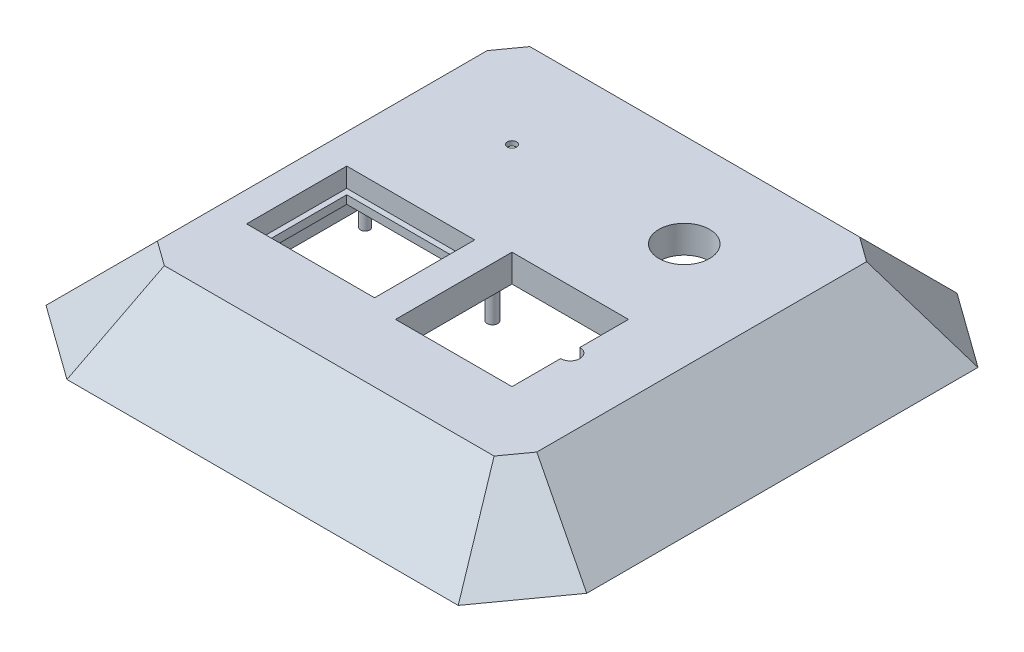
SolidWorks part; units mm, degrees
ref_plane "Front Plane" through (0, 0, 0) normal (0, 0, 1) x (1, 0, 0)
ref_plane "Top Plane" through (0, 0, 0) normal (0, 1, 0) x (1, 0, 0)
ref_plane "Right Plane" through (0, 0, 0) normal (1, 0, 0) x (0, 0, -1)
sketch "Sketch1" plane through (0, 0, 0) normal (0, 1, 0) x (1, 0, 0)
  line L0 (-47.3454, -21.7516) -> (37.6546, -21.7516)
  line L1 (37.6546, -21.7516) -> (49.3368, -5.5181)
  line L2 (49.3368, -5.5181) -> (49.3368, 79.4819)
  line L3 (49.3368, 79.4819) -> (33.1033, 91.1641)
  line L4 (33.1033, 91.1641) -> (-51.8967, 91.1641)
  line L5 (-51.8967, 91.1641) -> (-63.5789, 74.9306)
  line L6 (-63.5789, 74.9306) -> (-63.5789, -10.0694)
  line L7 (-63.5789, -10.0694) -> (-47.3454, -21.7516)
  dimension "D2" = 85
  dimension "D3" = 85
  dimension "D4" = 144.26
  dimension "D5" = 144.26
  dimension "D6" = 85
  dimension "D7" = 144.26
  dimension "D8" = 20
  dimension "D9" = 85
  dimension "D10" = 20
  dimension "D11" = 20
extrude "Boss-Extrude2" add sketch "Sketch1" along normal blind 16
sketch "Sketch4" plane through (0, 0, 0) normal (0, -1, 0) x (1, 0, 0)
  line L16 (-42.1868, 5.7516) -> (-47.5789, 1.8712)
  line L17 (-47.5789, 1.8712) -> (-47.5789, -69.772)
  line L18 (-47.5789, -69.772) -> (-43.6985, -75.1641)
  line L19 (-43.6985, -75.1641) -> (27.9447, -75.1641)
  line L20 (27.9447, -75.1641) -> (33.3368, -71.2838)
  line L21 (33.3368, -71.2838) -> (33.3368, 0.3594)
  line L22 (33.3368, 0.3594) -> (29.4564, 5.7516)
  line L23 (29.4564, 5.7516) -> (-42.1868, 5.7516)
  line L24 (-42.1868, 5.7516) -> (-47.5789, 1.8712)
  line L25 (-47.5789, 1.8712) -> (-47.5789, -69.772)
  line L26 (-47.5789, -69.772) -> (-43.6985, -75.1641)
  line L27 (-43.6985, -75.1641) -> (27.9447, -75.1641)
  line L28 (27.9447, -75.1641) -> (33.3368, -71.2838)
  line L29 (33.3368, -71.2838) -> (33.3368, 0.3594)
  line L30 (33.3368, 0.3594) -> (29.4564, 5.7516)
  line L31 (29.4564, 5.7516) -> (-42.1868, 5.7516)
  dimension "D1" = 16
chamfer "Chamfer1" distance 16 angle 45 8 edges at (-63.5789, 16, -32.4306) (-57.7378, 16, -83.0473) (-9.3967, 16, -91.1641) (41.22, 16, -85.323) (49.3368, 16, -36.9819) (43.4957, 16, 13.6348) (-4.8454, 16, 21.7516) (-55.4621, 16, 15.9105)
extrude "Cut-Extrude3" cut sketch "Sketch4" against normal blind 10
sketch "Sketch6" plane through (0, 16, 0) normal (0, 1, 0) x (1, 0, 0)
  line L0 (33.3368, -0.3594) -> (33.3368, 71.2838) construction
  line L1 (-6.9632, 34.5484) -> (18.3368, 34.5484)
  line L2 (-6.9632, 34.5484) -> (-6.9632, 9.2484)
  line L3 (-6.9632, 9.2484) -> (18.3368, 9.2484)
  line L4 (18.3368, 34.5484) -> (18.3368, 9.2484)
  line L5 (-42.1868, -5.7516) -> (29.4564, -5.7516) construction
  dimension "D1" = 25.3
  dimension "D2" = 25.3
  dimension "D3" = 15
  dimension "D4" = 15
extrude "Cut-Extrude4" cut sketch "Sketch6" against normal up to next
sketch "Sketch7" plane through (0, 10, 0) normal (0, -1, 0) x (1, 0, 0)
  line L0 (18.3368, -9.2484) -> (18.3368, -34.5484) construction
  circle A0 centre (18.3368, -21.8984) radius 2.0981
extrude "Cut-Extrude5" cut sketch "Sketch7" against normal up to next
sketch "Sketch8" plane through (0, 10, 0) normal (0, -1, 0) x (1, 0, 0)
  line L0 (-11.7632, -21.9984) -> (30.1662, -21.9984) construction
  line L1 (-11.7632, -8.8984) -> (24.2368, -8.8984)
  line L2 (-11.7632, -8.8984) -> (-11.7632, -35.0984)
  line L3 (-11.7632, -35.0984) -> (24.2368, -35.0984)
  line L4 (24.2368, -8.8984) -> (24.2368, -35.0984)
  line L5 (6.2368, -8.8984) -> (6.2368, -38.2867) construction
  line L6 (33.3368, -71.2838) -> (33.3368, 0.3594) construction
  line L7 (29.4564, 5.7516) -> (-42.1868, 5.7516) construction
  circle A0 centre (-9.2132, -11.4484) radius 1.15
  circle A1 centre (21.6868, -11.4484) radius 1.15
  circle A2 centre (21.6868, -32.5484) radius 1.15
  circle A3 centre (-9.2132, -32.5484) radius 1.15
  dimension "D3" = 2.3
  dimension "D4" = 2.55
  dimension "D5" = 2.55
  dimension "D6" = 9.1
  dimension "D1" = 36
  dimension "D2" = 26.2
  dimension "D7" = 14.65
extrude "Boss-Extrude3" add sketch "Sketch8" along normal blind 7 contours A0 | A1 | A2 | A3 region at (-9.2132, 10, -11.4484) region at (21.6868, 10, -11.4484) region at (21.6868, 10, -32.5484)
sketch "Sketch9" plane through (0, 10, 0) normal (0, -1, 0) x (1, 0, 0)
  line L2 (-47.5789, 1.8712) -> (-47.5789, -69.772) construction
  line L3 (-43.6985, -75.1641) -> (27.9447, -75.1641) construction
  circle A0 centre (-27.2189, -54.8041) radius 15.65
  dimension "D1" = 20.36
  dimension "D2" = 20.36
  dimension "D3" = 31.3
extrude "Cut-Extrude6" cut sketch "Sketch9" against normal blind 5
sketch "Sketch10" plane through (0, 15, 0) normal (0, -1, 0) x (1, 0, 0)
  circle A0 centre (-27.2189, -54.8041) radius 1
  dimension "D1" = 2
extrude "Cut-Extrude7" cut sketch "Sketch10" against normal up to next
sketch "Sketch11" plane through (0, 16, 0) normal (0, 1, 0) x (1, 0, 0)
  line L0 (-14.7144, 21.8984) -> (-6.9632, 21.8984) construction
  line L1 (-14.7144, 35.3984) -> (-39.7144, 35.3984)
  line L2 (-14.7144, 35.3984) -> (-14.7144, 8.3984)
  line L3 (-14.7144, 8.3984) -> (-39.7144, 8.3984)
  line L4 (-39.7144, 35.3984) -> (-39.7144, 8.3984)
  line L5 (-6.9632, 34.5484) -> (-6.9632, 9.2484) construction
  line L6 (-27.2144, 35.3984) -> (-27.2144, 2.0931) construction
  line L7 (-14.7144, 21.8984) -> (-44.3409, 21.8984) construction
  circle A0 centre (-37.5644, 33.2484) radius 1
  circle A1 centre (-16.8644, 33.2484) radius 1
  circle A2 centre (-16.8644, 10.5484) radius 1
  circle A3 centre (-37.5644, 10.5484) radius 1
  dimension "D3" = 2
  dimension "D4" = 2.15
  dimension "D5" = 2.15
  dimension "D1" = 25
  dimension "D2" = 27
extrude "Boss-Extrude4" add sketch "Sketch11" against normal blind 10 contours A0 | A1 | A2 | A3
sketch "Sketch12" plane through (0, 16, 0) normal (0, 1, 0) x (1, 0, 0)
  line L0 (-14.7144, 35.3984) -> (-14.7144, 8.3984) construction
  line L1 (-39.9144, 31.5984) -> (-14.5144, 31.5984)
  line L2 (-39.9144, 31.5984) -> (-39.9144, 12.2384)
  line L3 (-39.9144, 12.2384) -> (-14.5144, 12.2384)
  line L4 (-14.5144, 31.5984) -> (-14.5144, 12.2384)
  line L5 (-39.7144, 35.3984) -> (-39.7144, 8.3984) construction
  line L6 (-14.7144, 35.3984) -> (-39.7144, 35.3984) construction
  line L7 (-14.7144, 8.3984) -> (-39.7144, 8.3984) construction
  dimension "D1" = 0.2
  dimension "D2" = 0.2
  dimension "D3" = 3.8
  dimension "D4" = 3.84
extrude "Cut-Extrude8" cut sketch "Sketch12" against normal through all
sketch "Sketch13" plane through (0, 16, 0) normal (0, 1, 0) x (1, 0, 0)
  line L0 (-14.5144, 31.5984) -> (-39.9144, 31.5984) construction
  line L1 (-41.1144, 32.7984) -> (-13.3144, 32.7984)
  line L2 (-41.1144, 32.7984) -> (-41.1144, 11.0384)
  line L3 (-41.1144, 11.0384) -> (-13.3144, 11.0384)
  line L4 (-13.3144, 32.7984) -> (-13.3144, 11.0384)
  line L5 (-39.9144, 31.5984) -> (-39.9144, 12.2384) construction
  line L6 (-14.5144, 12.2384) -> (-14.5144, 31.5984) construction
  line L7 (-39.9144, 12.2384) -> (-14.5144, 12.2384) construction
  dimension "D1" = 1.2
  dimension "D2" = 1.2
  dimension "D3" = 1.2
  dimension "D4" = 1.2
extrude "Cut-Extrude9" cut sketch "Sketch13" against normal blind 4.2
sketch "Sketch14" plane through (0, 16, 0) normal (0, 1, 0) x (1, 0, 0)
  line L0 (10.2005, 54.8041) -> (-27.2189, 54.8041) construction
  circle A0 centre (10.2005, 54.8041) radius 5.5
extrude "Cut-Extrude10" cut sketch "Sketch14" against normal through all contours A0
